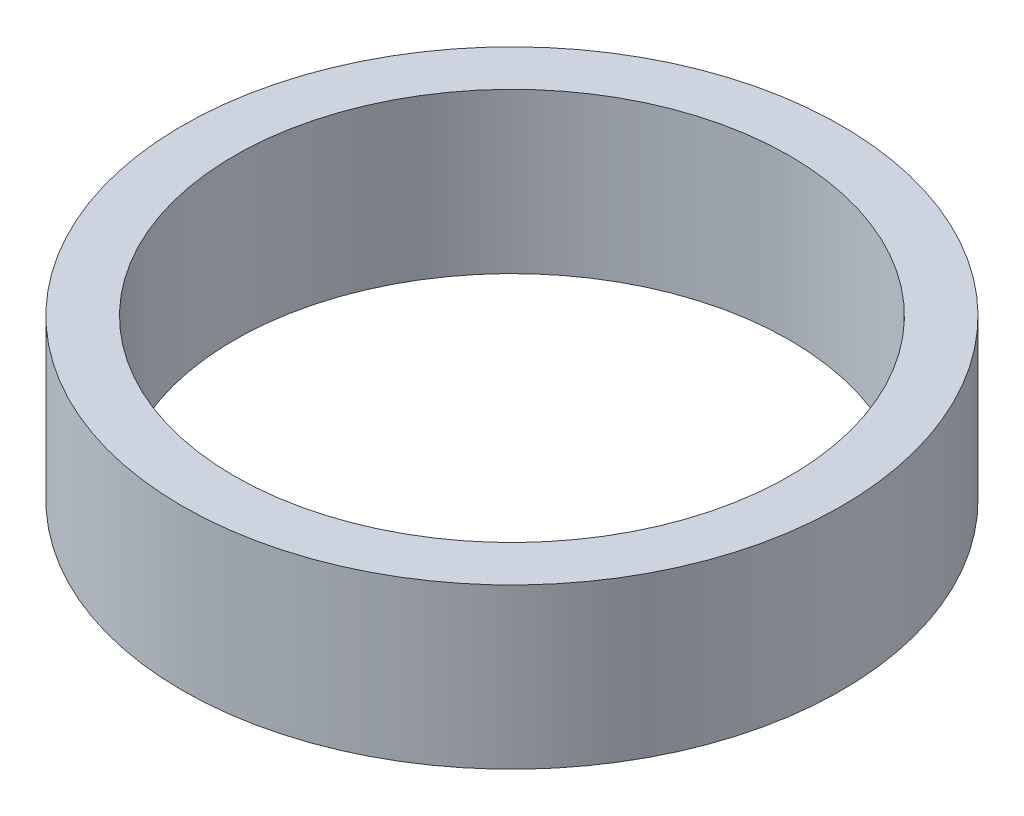
SolidWorks part; units mm, degrees
ref_plane "Front Plane" through (0, 0, 0) normal (0, 0, 1) x (1, 0, 0)
ref_plane "Top Plane" through (0, 0, 0) normal (0, 1, 0) x (1, 0, 0)
ref_plane "Right Plane" through (0, 0, 0) normal (1, 0, 0) x (0, 0, -1)
sketch "Sketch1" plane through (0, 0, 0) normal (0, 1, 0) x (1, 0, 0)
  circle A0 centre (0, 0) radius 47.5
  dimension "FLANGE_OD" = 95
extrude "Boss-Extrude1" add sketch "Sketch1" along normal blind 23
sketch "Sketch2" plane through (0, 0, 0) normal (0, 1, 0) x (1, 0, 0)
  circle A0 centre (0, 0) radius 40
  dimension "BORE_D" = 80
extrude "Cut-Extrude1" cut sketch "Sketch2" along normal through all
sketch "Sketch3" plane through (0, 23, 0) normal (0, 1, 0) x (1, 0, 0)
  circle A0 centre (0, 0) radius 21.3565 construction
  circle A1 centre (-21.3565, 0) radius 1.5
  dimension "BOLT_D" = 3
  dimension "BOLT_PCD" = 42.7131
extrude "Cut-Extrude2" cut sketch "Sketch3" against normal blind 15.9046 rebuild error yes
pattern_circular "CirPattern1" count 4 over 360 rebuild error yes
